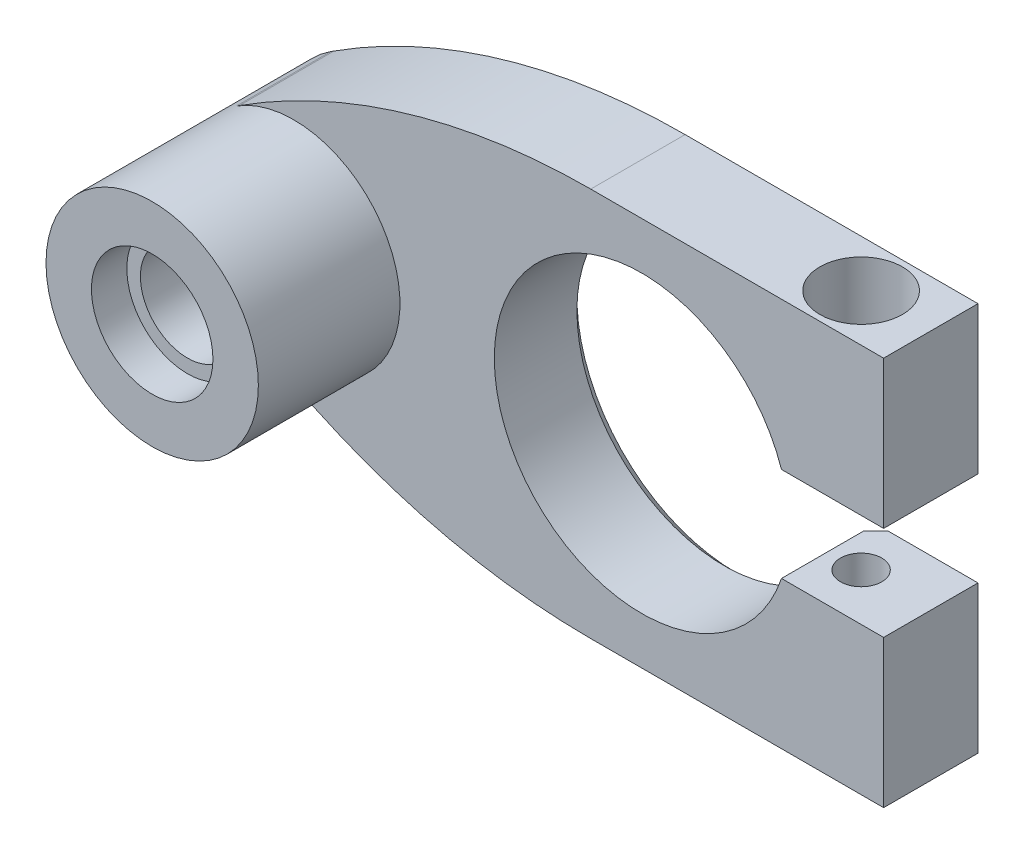
SolidWorks part; units mm, degrees
ref_plane "Plano frontal" through (0, 0, 0) normal (0, 0, 1) x (1, 0, 0)
ref_plane "Plano superior" through (0, 0, 0) normal (0, 1, 0) x (1, 0, 0)
ref_plane "Plano direito" through (0, 0, 0) normal (1, 0, 0) x (0, 0, -1)
sketch "Esboço1" plane through (0, 0, 0) normal (0, 0, 1) x (1, 0, 0)
  line L0 (-20.5, 16.5) -> (-34.3726, 7.5669)
  line L1 (-20.5, 16.5) -> (20.5, 16.5)
  line L2 (-20.5, 16.5) -> (-20.5, -16.5) construction
  line L3 (-20.5, -16.5) -> (20.5, -16.5)
  line L4 (20.5, 16.5) -> (20.5, 4)
  line L5 (-20.5, 16.5) -> (20.5, -16.5) construction
  line L6 (-20.5, -16.5) -> (20.5, 16.5) construction
  line L7 (-20.5, -16.5) -> (-34.3726, -7.5669)
  line L8 (20.5, 0) -> (9.3724, 0) construction
  line L9 (20.5, 4) -> (11.8427, 4)
  line L10 (20.5, -4) -> (11.8427, -4)
  line L11 (20.5, 4) -> (9.3724, 4) construction
  line L12 (20.5, -4) -> (9.3724, -4) construction
  line L13 (20.5, -4) -> (20.5, -16.5)
  arc A0 (-34.3726, 7.5669) -> (-34.3726, -7.5669) centre (-29.5, 0) ccw
  arc A1 (11.8427, 4) -> (11.8427, -4) centre (0, 0) ccw
  circle A2 centre (-29.5, 0) radius 4
  point P0 (0, 0)
  dimension "D1" = 18
  dimension "D2" = 25
  dimension "D5" = 8
  dimension "D3" = 4
  dimension "D4" = 8
  dimension "D6" = 4
  dimension "D7" = 4
extrude "Ressalto-extrusão1" add sketch "Esboço1" along normal blind 20
sketch "Esboço2" plane through (0, 0, 20) normal (0, 0, 1) x (1, 0, 0)
  circle A0 centre (-29.5, 0) radius 9
extrude "Corte-extrusão1" cut sketch "Esboço2" against normal blind 12 flip side to cut
fillet "Filete1" radius 55 2 edges at (-20.5, -16.5, 4) (-20.5, 16.5, 4)
sketch "Esboço3" plane through (0, 0, 20) normal (0, 0, 1) x (1, 0, 0)
  circle A0 centre (-29.5, 0) radius 5.15
  dimension "D1" = 10.3
extrude "Corte-extrusão2" cut sketch "Esboço3" against normal blind 3
extrude "Corte-extrusão3" cut sketch "Esboço3<2>" along normal blind 3 from surface starting at face at (-5.8033, 0, 0)
sketch "Esboço3<2>" plane through (0, 0, 20) normal (0, 0, 1) x (1, 0, 0) same geometry as "Esboço3"
sketch "Esboço4" plane through (0, -16.5, 0) normal (0, -1, 0) x (1, 0, 0)
  line L0 (11.8427, 8) -> (20.5, 0) construction
  circle A0 centre (14.5927, 4) radius 1.75
  point P0 (11.8427, 8)
  point P12 (16.1714, 4)
  dimension "D1" = 3.5
  dimension "D2" = 1
extrude "Corte-extrusão4" cut sketch "Esboço4" against normal through all
sketch "Esboço5" plane through (0, -16.5, 0) normal (0, -1, 0) x (1, 0, 0)
  line L1 (14.5927, 7.2332) -> (11.7927, 5.6166)
  line L2 (11.7927, 5.6166) -> (11.7927, 2.3834)
  line L3 (11.7927, 2.3834) -> (14.5927, 0.7668)
  line L4 (14.5927, 0.7668) -> (17.3927, 2.3834)
  line L5 (17.3927, 2.3834) -> (17.3927, 5.6166)
  line L6 (17.3927, 5.6166) -> (14.5927, 7.2332)
  circle A0 centre (14.5927, 4) radius 2.8 construction
  dimension "D1" = 5.6
extrude "Corte-extrusão5" cut sketch "Esboço5" against normal blind 7
sketch "Esboço6" plane through (0, 16.5, 0) normal (0, 1, 0) x (1, 0, 0)
  circle A0 centre (14.5927, -4) radius 3.5
  dimension "D1" = 7
extrude "Corte-extrusão6" cut sketch "Esboço6" against normal blind 5
chamfer "Chanfro1" distance 1 angle 45 2 edges at (-24.35, 0, 0) (-12.5, 0, 0)
